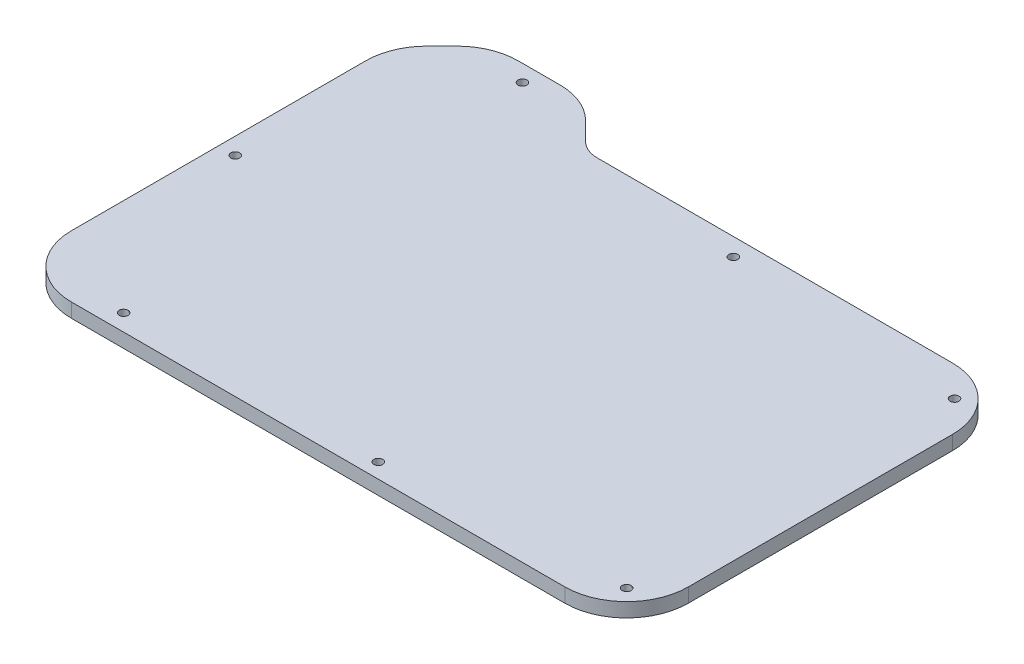
SolidWorks part; units mm, degrees
ref_plane "Front Plane" through (0, 0, 0) normal (0, 0, 1) x (1, 0, 0)
ref_plane "Top Plane" through (0, 0, 0) normal (0, 1, 0) x (1, 0, 0)
ref_plane "Right Plane" through (0, 0, 0) normal (1, 0, 0) x (0, 0, -1)
sketch "Sketch1" plane through (0, 0, 0) normal (0, 1, 0) x (1, 0, 0)
  line L14 (-185.1416, -125.2388) -> (-74.4068, -125.2388)
  line L15 (-60.5568, -111.3888) -> (-60.5568, -52.0888)
  line L16 (-74.4068, -38.2388) -> (-154.1313, -38.2388)
  line L17 (-158.6214, -36.379) -> (-162.705, -32.2954)
  line L18 (-172.4984, -28.2388) -> (-181.8614, -28.2388)
  line L19 (-191.6548, -32.2954) -> (-194.9351, -35.5756)
  line L20 (-198.9916, -45.3691) -> (-198.9916, -111.3888)
  arc A21 (-74.4068, -125.2388) -> (-60.5568, -111.3888) centre (-74.4068, -111.3888) ccw
  arc A22 (-60.5568, -52.0888) -> (-74.4068, -38.2388) centre (-74.4068, -52.0888) ccw
  arc A23 (-158.6214, -36.379) -> (-154.1313, -38.2388) centre (-154.1313, -31.8888) ccw
  arc A24 (-162.705, -32.2954) -> (-172.4984, -28.2388) centre (-172.4984, -42.0888) ccw
  arc A25 (-181.8614, -28.2388) -> (-191.6548, -32.2954) centre (-181.8614, -42.0888) ccw
  arc A26 (-194.9351, -35.5756) -> (-198.9916, -45.3691) centre (-185.1416, -45.3691) ccw
  arc A27 (-198.9916, -111.3888) -> (-185.1416, -125.2388) centre (-185.1416, -111.3888) ccw
  circle A28 centre (-67.265, -44.947) radius 1
  circle A29 centre (-67.265, -118.5306) radius 1
  circle A30 centre (-119.6281, -121.8847) radius 1
  circle A31 centre (-177.1799, -121.4888) radius 1
  circle A32 centre (-195.2416, -78.379) radius 1
  circle A33 centre (-177.1799, -31.9888) radius 1
  circle A34 centre (-119.6281, -42.2098) radius 1
extrude "Boss-Extrude1" add sketch "Sketch1" along normal blind 3.175
